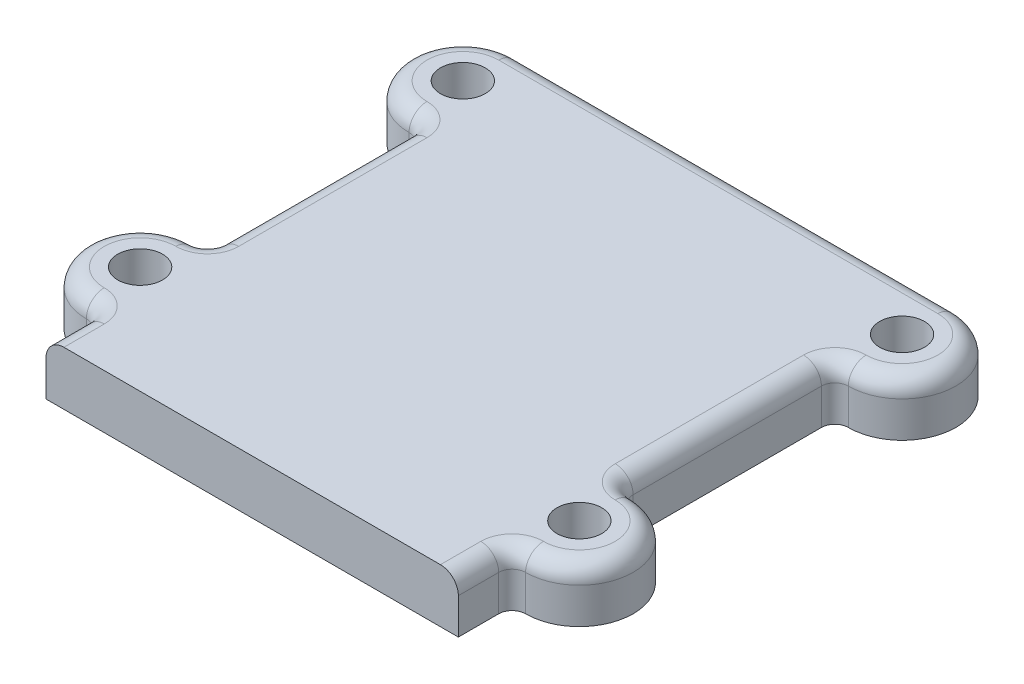
SolidWorks part; units mm, degrees
ref_plane "Front Plane" through (0, 0, 0) normal (0, 0, 1) x (1, 0, 0)
ref_plane "Top Plane" through (0, 0, 0) normal (0, 1, 0) x (1, 0, 0)
ref_plane "Right Plane" through (0, 0, 0) normal (1, 0, 0) x (0, 0, -1)
sketch "Sketch3" plane through (0, 0, 0) normal (0, 1, 0) x (1, 0, 0)
  line L13 (-11.5, -24) -> (-11.5, -27)
  line L19 (-11.5, -6) -> (-11.5, -18)
  line L23 (-12.25, -6) -> (-11.5, -6)
  line L25 (-12.25, -18) -> (-11.5, -18)
  line L27 (-12.25, -24) -> (-11.5, -24)
  line L37 (0, 0) -> (0, -27) construction
  line L38 (-12.25, 0) -> (12.25, 0)
  line L40 (-11.5, -27) -> (11.5, -27)
  line L45 (12.25, -24) -> (11.5, -24)
  line L46 (12.25, -18) -> (11.5, -18)
  line L47 (12.25, -6) -> (11.5, -6)
  line L48 (11.5, -6) -> (11.5, -18)
  line L49 (11.5, -24) -> (11.5, -27)
  arc A5 (-12.25, -18) -> (-12.25, -24) centre (-12.25, -21) ccw
  circle A6 centre (-12.25, -21) radius 1.25
  arc A7 (-12.25, 0) -> (-12.25, -6) centre (-12.25, -3) ccw
  circle A8 centre (-12.25, -3) radius 1.25
  circle A9 centre (12.25, -3) radius 1.25
  arc A10 (12.25, 0) -> (12.25, -6) centre (12.25, -3) cw
  circle A11 centre (12.25, -21) radius 1.25
  arc A12 (12.25, -18) -> (12.25, -24) centre (12.25, -21) cw
  dimension "D5" = 3
  dimension "D6" = 2.5
  dimension "D8" = 6
  dimension "D1" = 24.5
  dimension "D2" = 23
  dimension "D3" = 27
  dimension "D4" = 18
  dimension "D7" = 3
extrude "Boss-Extrude1" add sketch "Sketch3" along normal blind 3
fillet "Fillet1" radius 0.75 6 edges at (-11.5, 1.5, 18) (-11.5, 1.5, 24) (-11.5, 1.5, 6) (11.5, 1.5, 6) (11.5, 1.5, 24) (11.5, 1.5, 18)
fillet "Fillet2" radius 1 15 edges at (11.5, 3, 25.875) (11.7197, 3, 24.2197) (15.25, 3, 21) (11.7197, 3, 17.7803) (-11.5, 3, 25.875) (-11.7197, 3, 24.2197) (-15.25, 3, 21) (-11.7197, 3, 17.7803) (-11.5, 3, 12) (-11.7197, 3, 6.2197) (-15.25, 3, 3) (0, 3, 0) (15.25, 3, 3) (11.7197, 3, 6.2197) (11.5, 3, 12)
